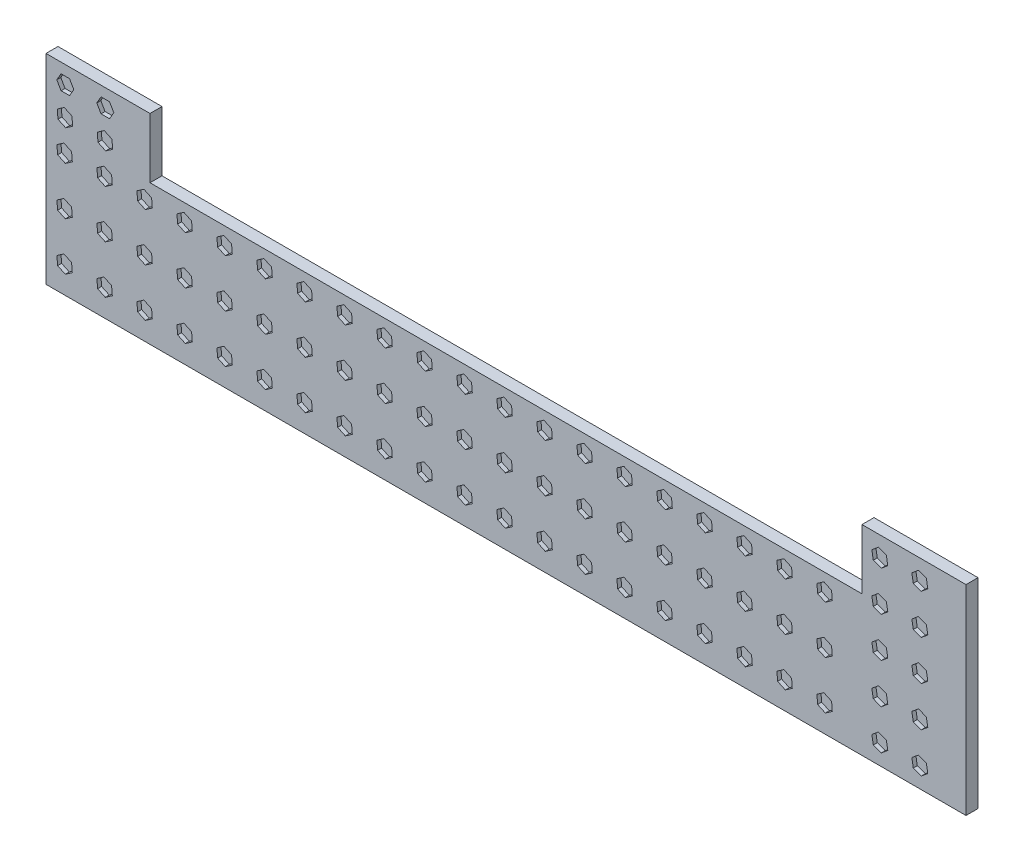
SolidWorks part; units mm, degrees
ref_plane "Front Plane" through (0, 0, 0) normal (0, 0, 1) x (1, 0, 0)
ref_plane "Top Plane" through (0, 0, 0) normal (0, 1, 0) x (1, 0, 0)
ref_plane "Right Plane" through (0, 0, 0) normal (1, 0, 0) x (0, 0, -1)
sketch "Sketch1" plane through (0, 0, 0) normal (0, 0, 1) x (1, 0, 0)
  line L6 (-151.2957, 20.8865) -> (-151.2957, -29.1135)
  line L7 (-151.2957, -29.1135) -> (78.7043, -29.1135)
  line L9 (78.7043, 20.8865) -> (78.7043, -29.1135)
  line L10 (-151.2957, 20.8865) -> (-125.2957, 20.8865)
  line L11 (-125.2957, 20.8865) -> (-125.2957, 5.8865)
  line L12 (-125.2957, 5.8865) -> (52.7043, 5.8865)
  line L13 (52.7043, 5.8865) -> (52.7043, 20.8865)
  line L14 (52.7043, 20.8865) -> (78.7043, 20.8865)
  dimension "D1" = 230
  dimension "D2" = 26
  dimension "D3" = 15
  dimension "D4" = 50
extrude "Boss-Extrude1" add sketch "Sketch1" along normal blind 3
sketch "Sketch2" plane through (0, 0, 3) normal (0, 0, 1) x (1, 0, 0)
  line L0 (69.1519, 15.1967) -> (68.7905, 17.2904)
  line L1 (-144.3473, 16.5251) -> (-145.4096, 18.3651)
  line L2 (-145.4096, 18.3651) -> (-147.5343, 18.3651)
  line L3 (-147.5343, 18.3651) -> (-148.5966, 16.5251)
  line L4 (-148.5966, 16.5251) -> (-147.5343, 14.6851)
  line L5 (-147.5343, 14.6851) -> (-145.4096, 14.6851)
  line L6 (-145.4096, 14.6851) -> (-144.3473, 16.5251)
  line L7 (59.1519, 15.1967) -> (58.7905, 17.2904)
  line L8 (58.7905, 17.2904) -> (56.7966, 18.0243)
  line L9 (56.7966, 18.0243) -> (55.1642, 16.6645)
  line L10 (55.1642, 16.6645) -> (55.5255, 14.5708)
  line L11 (55.5255, 14.5708) -> (57.5194, 13.8369)
  line L12 (57.5194, 13.8369) -> (59.1519, 15.1967)
  line L13 (-144.6353, 8.4459) -> (-144.813, 10.5631)
  line L14 (-144.813, 10.5631) -> (-146.7355, 11.4677)
  line L15 (-146.7355, 11.4677) -> (-148.4801, 10.2552)
  line L16 (-148.4801, 10.2552) -> (-148.3024, 8.138)
  line L17 (-148.3024, 8.138) -> (-146.38, 7.2333)
  line L18 (-146.38, 7.2333) -> (-144.6353, 8.4459)
  line L19 (68.7905, 17.2904) -> (66.7966, 18.0243)
  line L20 (66.7966, 18.0243) -> (65.1642, 16.6645)
  line L21 (65.1642, 16.6645) -> (65.5255, 14.5708)
  line L22 (65.5255, 14.5708) -> (67.5194, 13.8369)
  line L23 (67.5194, 13.8369) -> (69.1519, 15.1967)
  line L24 (69.1519, 5.1967) -> (68.7905, 7.2904)
  line L25 (68.7905, 7.2904) -> (66.7966, 8.0243)
  line L26 (66.7966, 8.0243) -> (65.1642, 6.6645)
  line L27 (65.1642, 6.6645) -> (65.5255, 4.5708)
  line L28 (65.5255, 4.5708) -> (67.5194, 3.8369)
  line L29 (67.5194, 3.8369) -> (69.1519, 5.1967)
  line L30 (69.1519, -4.8033) -> (68.7905, -2.7096)
  line L31 (68.7905, -2.7096) -> (66.7966, -1.9757)
  line L32 (66.7966, -1.9757) -> (65.1642, -3.3355)
  line L33 (65.1642, -3.3355) -> (65.5255, -5.4292)
  line L34 (65.5255, -5.4292) -> (67.5194, -6.1631)
  line L35 (67.5194, -6.1631) -> (69.1519, -4.8033)
  line L36 (69.1519, -14.8033) -> (68.7905, -12.7096)
  line L37 (68.7905, -12.7096) -> (66.7966, -11.9757)
  line L38 (66.7966, -11.9757) -> (65.1642, -13.3355)
  line L39 (65.1642, -13.3355) -> (65.5255, -15.4292)
  line L40 (65.5255, -15.4292) -> (67.5194, -16.1631)
  line L41 (67.5194, -16.1631) -> (69.1519, -14.8033)
  line L42 (69.1519, -24.8033) -> (68.7905, -22.7096)
  line L43 (68.7905, -22.7096) -> (66.7966, -21.9757)
  line L44 (66.7966, -21.9757) -> (65.1642, -23.3355)
  line L45 (65.1642, -23.3355) -> (65.5255, -25.4292)
  line L46 (65.5255, -25.4292) -> (67.5194, -26.1631)
  line L47 (67.5194, -26.1631) -> (69.1519, -24.8033)
  line L48 (59.1519, 5.1967) -> (58.7905, 7.2904)
  line L49 (58.7905, 7.2904) -> (56.7966, 8.0243)
  line L50 (56.7966, 8.0243) -> (55.1642, 6.6645)
  line L51 (55.1642, 6.6645) -> (55.5255, 4.5708)
  line L52 (55.5255, 4.5708) -> (57.5194, 3.8369)
  line L53 (57.5194, 3.8369) -> (59.1519, 5.1967)
  line L54 (59.1519, -4.8033) -> (58.7905, -2.7096)
  line L55 (58.7905, -2.7096) -> (56.7966, -1.9757)
  line L56 (56.7966, -1.9757) -> (55.1642, -3.3355)
  line L57 (55.1642, -3.3355) -> (55.5255, -5.4292)
  line L58 (55.5255, -5.4292) -> (57.5194, -6.1631)
  line L59 (57.5194, -6.1631) -> (59.1519, -4.8033)
  line L60 (59.1519, -14.8033) -> (58.7905, -12.7096)
  line L61 (58.7905, -12.7096) -> (56.7966, -11.9757)
  line L62 (56.7966, -11.9757) -> (55.1642, -13.3355)
  line L63 (55.1642, -13.3355) -> (55.5255, -15.4292)
  line L64 (55.5255, -15.4292) -> (57.5194, -16.1631)
  line L65 (57.5194, -16.1631) -> (59.1519, -14.8033)
  line L66 (59.1519, -24.8033) -> (58.7905, -22.7096)
  line L67 (58.7905, -22.7096) -> (56.7966, -21.9757)
  line L68 (56.7966, -21.9757) -> (55.1642, -23.3355)
  line L69 (55.1642, -23.3355) -> (55.5255, -25.4292)
  line L70 (55.5255, -25.4292) -> (57.5194, -26.1631)
  line L71 (57.5194, -26.1631) -> (59.1519, -24.8033)
  line L72 (-144.7223, 0.6978) -> (-144.9001, 2.815)
  line L73 (-144.9001, 2.815) -> (-146.8225, 3.7197)
  line L74 (-146.8225, 3.7197) -> (-148.5672, 2.5072)
  line L75 (-148.5672, 2.5072) -> (-148.3894, 0.39)
  line L76 (-148.3894, 0.39) -> (-146.467, -0.5147)
  line L77 (-146.467, -0.5147) -> (-144.7223, 0.6978)
  line L78 (-134.3473, 16.5251) -> (-135.4096, 18.3651)
  line L79 (-135.4096, 18.3651) -> (-137.5343, 18.3651)
  line L80 (-137.5343, 18.3651) -> (-138.5966, 16.5251)
  line L81 (-138.5966, 16.5251) -> (-137.5343, 14.6851)
  line L82 (-137.5343, 14.6851) -> (-135.4096, 14.6851)
  line L83 (-135.4096, 14.6851) -> (-134.3473, 16.5251)
  line L84 (-134.6353, 8.4459) -> (-134.813, 10.5631)
  line L85 (-134.813, 10.5631) -> (-136.7355, 11.4677)
  line L86 (-136.7355, 11.4677) -> (-138.4801, 10.2552)
  line L87 (-138.4801, 10.2552) -> (-138.3024, 8.138)
  line L88 (-138.3024, 8.138) -> (-136.38, 7.2333)
  line L89 (-136.38, 7.2333) -> (-134.6353, 8.4459)
  line L90 (-134.7223, 0.6978) -> (-134.9001, 2.815)
  line L91 (-134.9001, 2.815) -> (-136.8225, 3.7197)
  line L92 (-136.8225, 3.7197) -> (-138.5672, 2.5072)
  line L93 (-138.5672, 2.5072) -> (-138.3894, 0.39)
  line L94 (-138.3894, 0.39) -> (-136.467, -0.5147)
  line L95 (-136.467, -0.5147) -> (-134.7223, 0.6978)
  line L96 (-124.7223, 0.6978) -> (-124.9001, 2.815)
  line L97 (-124.9001, 2.815) -> (-126.8225, 3.7197)
  line L98 (-126.8225, 3.7197) -> (-128.5672, 2.5072)
  line L99 (-128.5672, 2.5072) -> (-128.3894, 0.39)
  line L100 (-128.3894, 0.39) -> (-126.467, -0.5147)
  line L101 (-126.467, -0.5147) -> (-124.7223, 0.6978)
  line L102 (-114.7223, 0.6978) -> (-114.9001, 2.815)
  line L103 (-114.9001, 2.815) -> (-116.8225, 3.7197)
  line L104 (-116.8225, 3.7197) -> (-118.5672, 2.5072)
  line L105 (-118.5672, 2.5072) -> (-118.3894, 0.39)
  line L106 (-118.3894, 0.39) -> (-116.467, -0.5147)
  line L107 (-116.467, -0.5147) -> (-114.7223, 0.6978)
  line L108 (-104.7223, 0.6978) -> (-104.9001, 2.815)
  line L109 (-104.9001, 2.815) -> (-106.8225, 3.7197)
  line L110 (-106.8225, 3.7197) -> (-108.5672, 2.5072)
  line L111 (-108.5672, 2.5072) -> (-108.3894, 0.39)
  line L112 (-108.3894, 0.39) -> (-106.467, -0.5147)
  line L113 (-106.467, -0.5147) -> (-104.7223, 0.6978)
  line L114 (-94.7223, 0.6978) -> (-94.9001, 2.815)
  line L115 (-94.9001, 2.815) -> (-96.8225, 3.7197)
  line L116 (-96.8225, 3.7197) -> (-98.5672, 2.5072)
  line L117 (-98.5672, 2.5072) -> (-98.3894, 0.39)
  line L118 (-98.3894, 0.39) -> (-96.467, -0.5147)
  line L119 (-96.467, -0.5147) -> (-94.7223, 0.6978)
  line L120 (-84.7223, 0.6978) -> (-84.9001, 2.815)
  line L121 (-84.9001, 2.815) -> (-86.8225, 3.7197)
  line L122 (-86.8225, 3.7197) -> (-88.5672, 2.5072)
  line L123 (-88.5672, 2.5072) -> (-88.3894, 0.39)
  line L124 (-88.3894, 0.39) -> (-86.467, -0.5147)
  line L125 (-86.467, -0.5147) -> (-84.7223, 0.6978)
  line L126 (-74.7223, 0.6978) -> (-74.9001, 2.815)
  line L127 (-74.9001, 2.815) -> (-76.8225, 3.7197)
  line L128 (-76.8225, 3.7197) -> (-78.5672, 2.5072)
  line L129 (-78.5672, 2.5072) -> (-78.3894, 0.39)
  line L130 (-78.3894, 0.39) -> (-76.467, -0.5147)
  line L131 (-76.467, -0.5147) -> (-74.7223, 0.6978)
  line L132 (-64.7223, 0.6978) -> (-64.9001, 2.815)
  line L133 (-64.9001, 2.815) -> (-66.8225, 3.7197)
  line L134 (-66.8225, 3.7197) -> (-68.5672, 2.5072)
  line L135 (-68.5672, 2.5072) -> (-68.3894, 0.39)
  line L136 (-68.3894, 0.39) -> (-66.467, -0.5147)
  line L137 (-66.467, -0.5147) -> (-64.7223, 0.6978)
  line L138 (-54.7223, 0.6978) -> (-54.9001, 2.815)
  line L139 (-54.9001, 2.815) -> (-56.8225, 3.7197)
  line L140 (-56.8225, 3.7197) -> (-58.5672, 2.5072)
  line L141 (-58.5672, 2.5072) -> (-58.3894, 0.39)
  line L142 (-58.3894, 0.39) -> (-56.467, -0.5147)
  line L143 (-56.467, -0.5147) -> (-54.7223, 0.6978)
  line L144 (-44.7223, 0.6978) -> (-44.9001, 2.815)
  line L145 (-44.9001, 2.815) -> (-46.8225, 3.7197)
  line L146 (-46.8225, 3.7197) -> (-48.5672, 2.5072)
  line L147 (-48.5672, 2.5072) -> (-48.3894, 0.39)
  line L148 (-48.3894, 0.39) -> (-46.467, -0.5147)
  line L149 (-46.467, -0.5147) -> (-44.7223, 0.6978)
  line L150 (-34.7223, 0.6978) -> (-34.9001, 2.815)
  line L151 (-34.9001, 2.815) -> (-36.8225, 3.7197)
  line L152 (-36.8225, 3.7197) -> (-38.5672, 2.5072)
  line L153 (-38.5672, 2.5072) -> (-38.3894, 0.39)
  line L154 (-38.3894, 0.39) -> (-36.467, -0.5147)
  line L155 (-36.467, -0.5147) -> (-34.7223, 0.6978)
  line L156 (-24.7223, 0.6978) -> (-24.9001, 2.815)
  line L157 (-24.9001, 2.815) -> (-26.8225, 3.7197)
  line L158 (-26.8225, 3.7197) -> (-28.5672, 2.5072)
  line L159 (-28.5672, 2.5072) -> (-28.3894, 0.39)
  line L160 (-28.3894, 0.39) -> (-26.467, -0.5147)
  line L161 (-26.467, -0.5147) -> (-24.7223, 0.6978)
  line L162 (-14.7223, 0.6978) -> (-14.9001, 2.815)
  line L163 (-14.9001, 2.815) -> (-16.8225, 3.7197)
  line L164 (-16.8225, 3.7197) -> (-18.5672, 2.5072)
  line L165 (-18.5672, 2.5072) -> (-18.3894, 0.39)
  line L166 (-18.3894, 0.39) -> (-16.467, -0.5147)
  line L167 (-16.467, -0.5147) -> (-14.7223, 0.6978)
  line L168 (-4.7223, 0.6978) -> (-4.9001, 2.815)
  line L169 (-4.9001, 2.815) -> (-6.8225, 3.7197)
  line L170 (-6.8225, 3.7197) -> (-8.5672, 2.5072)
  line L171 (-8.5672, 2.5072) -> (-8.3894, 0.39)
  line L172 (-8.3894, 0.39) -> (-6.467, -0.5147)
  line L173 (-6.467, -0.5147) -> (-4.7223, 0.6978)
  line L174 (5.2777, 0.6978) -> (5.0999, 2.815)
  line L175 (5.0999, 2.815) -> (3.1775, 3.7197)
  line L176 (3.1775, 3.7197) -> (1.4328, 2.5072)
  line L177 (1.4328, 2.5072) -> (1.6106, 0.39)
  line L178 (1.6106, 0.39) -> (3.533, -0.5147)
  line L179 (3.533, -0.5147) -> (5.2777, 0.6978)
  line L180 (15.2777, 0.6978) -> (15.0999, 2.815)
  line L181 (15.0999, 2.815) -> (13.1775, 3.7197)
  line L182 (13.1775, 3.7197) -> (11.4328, 2.5072)
  line L183 (11.4328, 2.5072) -> (11.6106, 0.39)
  line L184 (11.6106, 0.39) -> (13.533, -0.5147)
  line L185 (13.533, -0.5147) -> (15.2777, 0.6978)
  line L186 (25.2777, 0.6978) -> (25.0999, 2.815)
  line L187 (25.0999, 2.815) -> (23.1775, 3.7197)
  line L188 (23.1775, 3.7197) -> (21.4328, 2.5072)
  line L189 (21.4328, 2.5072) -> (21.6106, 0.39)
  line L190 (21.6106, 0.39) -> (23.533, -0.5147)
  line L191 (23.533, -0.5147) -> (25.2777, 0.6978)
  line L192 (35.2777, 0.6978) -> (35.0999, 2.815)
  line L193 (35.0999, 2.815) -> (33.1775, 3.7197)
  line L194 (33.1775, 3.7197) -> (31.4328, 2.5072)
  line L195 (31.4328, 2.5072) -> (31.6106, 0.39)
  line L196 (31.6106, 0.39) -> (33.533, -0.5147)
  line L197 (33.533, -0.5147) -> (35.2777, 0.6978)
  line L198 (45.2777, 0.6978) -> (45.0999, 2.815)
  line L199 (45.0999, 2.815) -> (43.1775, 3.7197)
  line L200 (43.1775, 3.7197) -> (41.4328, 2.5072)
  line L201 (41.4328, 2.5072) -> (41.6106, 0.39)
  line L202 (41.6106, 0.39) -> (43.533, -0.5147)
  line L203 (43.533, -0.5147) -> (45.2777, 0.6978)
  line L204 (-134.7223, -11.3022) -> (-134.9001, -9.185)
  line L205 (-134.9001, -9.185) -> (-136.8225, -8.2803)
  line L206 (-136.8225, -8.2803) -> (-138.5672, -9.4928)
  line L207 (-138.5672, -9.4928) -> (-138.3894, -11.61)
  line L208 (-138.3894, -11.61) -> (-136.467, -12.5147)
  line L209 (-136.467, -12.5147) -> (-134.7223, -11.3022)
  line L210 (-124.7223, -11.3022) -> (-124.9001, -9.185)
  line L211 (-124.9001, -9.185) -> (-126.8225, -8.2803)
  line L212 (-126.8225, -8.2803) -> (-128.5672, -9.4928)
  line L213 (-128.5672, -9.4928) -> (-128.3894, -11.61)
  line L214 (-128.3894, -11.61) -> (-126.467, -12.5147)
  line L215 (-126.467, -12.5147) -> (-124.7223, -11.3022)
  line L216 (-114.7223, -11.3022) -> (-114.9001, -9.185)
  line L217 (-114.9001, -9.185) -> (-116.8225, -8.2803)
  line L218 (-116.8225, -8.2803) -> (-118.5672, -9.4928)
  line L219 (-118.5672, -9.4928) -> (-118.3894, -11.61)
  line L220 (-118.3894, -11.61) -> (-116.467, -12.5147)
  line L221 (-116.467, -12.5147) -> (-114.7223, -11.3022)
  line L222 (-104.7223, -11.3022) -> (-104.9001, -9.185)
  line L223 (-104.9001, -9.185) -> (-106.8225, -8.2803)
  line L224 (-106.8225, -8.2803) -> (-108.5672, -9.4928)
  line L225 (-108.5672, -9.4928) -> (-108.3894, -11.61)
  line L226 (-108.3894, -11.61) -> (-106.467, -12.5147)
  line L227 (-106.467, -12.5147) -> (-104.7223, -11.3022)
  line L228 (-94.7223, -11.3022) -> (-94.9001, -9.185)
  line L229 (-94.9001, -9.185) -> (-96.8225, -8.2803)
  line L230 (-96.8225, -8.2803) -> (-98.5672, -9.4928)
  line L231 (-98.5672, -9.4928) -> (-98.3894, -11.61)
  line L232 (-98.3894, -11.61) -> (-96.467, -12.5147)
  line L233 (-96.467, -12.5147) -> (-94.7223, -11.3022)
  line L234 (-84.7223, -11.3022) -> (-84.9001, -9.185)
  line L235 (-84.9001, -9.185) -> (-86.8225, -8.2803)
  line L236 (-86.8225, -8.2803) -> (-88.5672, -9.4928)
  line L237 (-88.5672, -9.4928) -> (-88.3894, -11.61)
  line L238 (-88.3894, -11.61) -> (-86.467, -12.5147)
  line L239 (-86.467, -12.5147) -> (-84.7223, -11.3022)
  line L240 (-74.7223, -11.3022) -> (-74.9001, -9.185)
  line L241 (-74.9001, -9.185) -> (-76.8225, -8.2803)
  line L242 (-76.8225, -8.2803) -> (-78.5672, -9.4928)
  line L243 (-78.5672, -9.4928) -> (-78.3894, -11.61)
  line L244 (-78.3894, -11.61) -> (-76.467, -12.5147)
  line L245 (-76.467, -12.5147) -> (-74.7223, -11.3022)
  line L246 (-64.7223, -11.3022) -> (-64.9001, -9.185)
  line L247 (-64.9001, -9.185) -> (-66.8225, -8.2803)
  line L248 (-66.8225, -8.2803) -> (-68.5672, -9.4928)
  line L249 (-68.5672, -9.4928) -> (-68.3894, -11.61)
  line L250 (-68.3894, -11.61) -> (-66.467, -12.5147)
  line L251 (-66.467, -12.5147) -> (-64.7223, -11.3022)
  line L252 (-54.7223, -11.3022) -> (-54.9001, -9.185)
  line L253 (-54.9001, -9.185) -> (-56.8225, -8.2803)
  line L254 (-56.8225, -8.2803) -> (-58.5672, -9.4928)
  line L255 (-58.5672, -9.4928) -> (-58.3894, -11.61)
  line L256 (-58.3894, -11.61) -> (-56.467, -12.5147)
  line L257 (-56.467, -12.5147) -> (-54.7223, -11.3022)
  line L258 (-44.7223, -11.3022) -> (-44.9001, -9.185)
  line L259 (-44.9001, -9.185) -> (-46.8225, -8.2803)
  line L260 (-46.8225, -8.2803) -> (-48.5672, -9.4928)
  line L261 (-48.5672, -9.4928) -> (-48.3894, -11.61)
  line L262 (-48.3894, -11.61) -> (-46.467, -12.5147)
  line L263 (-46.467, -12.5147) -> (-44.7223, -11.3022)
  line L264 (-34.7223, -11.3022) -> (-34.9001, -9.185)
  line L265 (-34.9001, -9.185) -> (-36.8225, -8.2803)
  line L266 (-36.8225, -8.2803) -> (-38.5672, -9.4928)
  line L267 (-38.5672, -9.4928) -> (-38.3894, -11.61)
  line L268 (-38.3894, -11.61) -> (-36.467, -12.5147)
  line L269 (-36.467, -12.5147) -> (-34.7223, -11.3022)
  line L270 (-24.7223, -11.3022) -> (-24.9001, -9.185)
  line L271 (-24.9001, -9.185) -> (-26.8225, -8.2803)
  line L272 (-26.8225, -8.2803) -> (-28.5672, -9.4928)
  line L273 (-28.5672, -9.4928) -> (-28.3894, -11.61)
  line L274 (-28.3894, -11.61) -> (-26.467, -12.5147)
  line L275 (-26.467, -12.5147) -> (-24.7223, -11.3022)
  line L276 (-14.7223, -11.3022) -> (-14.9001, -9.185)
  line L277 (-14.9001, -9.185) -> (-16.8225, -8.2803)
  line L278 (-16.8225, -8.2803) -> (-18.5672, -9.4928)
  line L279 (-18.5672, -9.4928) -> (-18.3894, -11.61)
  line L280 (-18.3894, -11.61) -> (-16.467, -12.5147)
  line L281 (-16.467, -12.5147) -> (-14.7223, -11.3022)
  line L282 (-4.7223, -11.3022) -> (-4.9001, -9.185)
  line L283 (-4.9001, -9.185) -> (-6.8225, -8.2803)
  line L284 (-6.8225, -8.2803) -> (-8.5672, -9.4928)
  line L285 (-8.5672, -9.4928) -> (-8.3894, -11.61)
  line L286 (-8.3894, -11.61) -> (-6.467, -12.5147)
  line L287 (-6.467, -12.5147) -> (-4.7223, -11.3022)
  line L288 (5.2777, -11.3022) -> (5.0999, -9.185)
  line L289 (5.0999, -9.185) -> (3.1775, -8.2803)
  line L290 (3.1775, -8.2803) -> (1.4328, -9.4928)
  line L291 (1.4328, -9.4928) -> (1.6106, -11.61)
  line L292 (1.6106, -11.61) -> (3.533, -12.5147)
  line L293 (3.533, -12.5147) -> (5.2777, -11.3022)
  line L294 (15.2777, -11.3022) -> (15.0999, -9.185)
  line L295 (15.0999, -9.185) -> (13.1775, -8.2803)
  line L296 (13.1775, -8.2803) -> (11.4328, -9.4928)
  line L297 (11.4328, -9.4928) -> (11.6106, -11.61)
  line L298 (11.6106, -11.61) -> (13.533, -12.5147)
  line L299 (13.533, -12.5147) -> (15.2777, -11.3022)
  line L300 (25.2777, -11.3022) -> (25.0999, -9.185)
  line L301 (25.0999, -9.185) -> (23.1775, -8.2803)
  line L302 (23.1775, -8.2803) -> (21.4328, -9.4928)
  line L303 (21.4328, -9.4928) -> (21.6106, -11.61)
  line L304 (21.6106, -11.61) -> (23.533, -12.5147)
  line L305 (23.533, -12.5147) -> (25.2777, -11.3022)
  line L306 (35.2777, -11.3022) -> (35.0999, -9.185)
  line L307 (35.0999, -9.185) -> (33.1775, -8.2803)
  line L308 (33.1775, -8.2803) -> (31.4328, -9.4928)
  line L309 (31.4328, -9.4928) -> (31.6106, -11.61)
  line L310 (31.6106, -11.61) -> (33.533, -12.5147)
  line L311 (33.533, -12.5147) -> (35.2777, -11.3022)
  line L312 (45.2777, -11.3022) -> (45.0999, -9.185)
  line L313 (45.0999, -9.185) -> (43.1775, -8.2803)
  line L314 (43.1775, -8.2803) -> (41.4328, -9.4928)
  line L315 (41.4328, -9.4928) -> (41.6106, -11.61)
  line L316 (41.6106, -11.61) -> (43.533, -12.5147)
  line L317 (43.533, -12.5147) -> (45.2777, -11.3022)
  line L318 (-134.7223, -23.3022) -> (-134.9001, -21.185)
  line L319 (-134.9001, -21.185) -> (-136.8225, -20.2803)
  line L320 (-136.8225, -20.2803) -> (-138.5672, -21.4928)
  line L321 (-138.5672, -21.4928) -> (-138.3894, -23.61)
  line L322 (-138.3894, -23.61) -> (-136.467, -24.5147)
  line L323 (-136.467, -24.5147) -> (-134.7223, -23.3022)
  line L324 (-124.7223, -23.3022) -> (-124.9001, -21.185)
  line L325 (-124.9001, -21.185) -> (-126.8225, -20.2803)
  line L326 (-126.8225, -20.2803) -> (-128.5672, -21.4928)
  line L327 (-128.5672, -21.4928) -> (-128.3894, -23.61)
  line L328 (-128.3894, -23.61) -> (-126.467, -24.5147)
  line L329 (-126.467, -24.5147) -> (-124.7223, -23.3022)
  line L330 (-114.7223, -23.3022) -> (-114.9001, -21.185)
  line L331 (-114.9001, -21.185) -> (-116.8225, -20.2803)
  line L332 (-116.8225, -20.2803) -> (-118.5672, -21.4928)
  line L333 (-118.5672, -21.4928) -> (-118.3894, -23.61)
  line L334 (-118.3894, -23.61) -> (-116.467, -24.5147)
  line L335 (-116.467, -24.5147) -> (-114.7223, -23.3022)
  line L336 (-104.7223, -23.3022) -> (-104.9001, -21.185)
  line L337 (-104.9001, -21.185) -> (-106.8225, -20.2803)
  line L338 (-106.8225, -20.2803) -> (-108.5672, -21.4928)
  line L339 (-108.5672, -21.4928) -> (-108.3894, -23.61)
  line L340 (-108.3894, -23.61) -> (-106.467, -24.5147)
  line L341 (-106.467, -24.5147) -> (-104.7223, -23.3022)
  line L342 (-94.7223, -23.3022) -> (-94.9001, -21.185)
  line L343 (-94.9001, -21.185) -> (-96.8225, -20.2803)
  line L344 (-96.8225, -20.2803) -> (-98.5672, -21.4928)
  line L345 (-98.5672, -21.4928) -> (-98.3894, -23.61)
  line L346 (-98.3894, -23.61) -> (-96.467, -24.5147)
  line L347 (-96.467, -24.5147) -> (-94.7223, -23.3022)
  line L348 (-84.7223, -23.3022) -> (-84.9001, -21.185)
  line L349 (-84.9001, -21.185) -> (-86.8225, -20.2803)
  line L350 (-86.8225, -20.2803) -> (-88.5672, -21.4928)
  line L351 (-88.5672, -21.4928) -> (-88.3894, -23.61)
  line L352 (-88.3894, -23.61) -> (-86.467, -24.5147)
  line L353 (-86.467, -24.5147) -> (-84.7223, -23.3022)
  line L354 (-74.7223, -23.3022) -> (-74.9001, -21.185)
  line L355 (-74.9001, -21.185) -> (-76.8225, -20.2803)
  line L356 (-76.8225, -20.2803) -> (-78.5672, -21.4928)
  line L357 (-78.5672, -21.4928) -> (-78.3894, -23.61)
  line L358 (-78.3894, -23.61) -> (-76.467, -24.5147)
  line L359 (-76.467, -24.5147) -> (-74.7223, -23.3022)
  line L360 (-64.7223, -23.3022) -> (-64.9001, -21.185)
  line L361 (-64.9001, -21.185) -> (-66.8225, -20.2803)
  line L362 (-66.8225, -20.2803) -> (-68.5672, -21.4928)
  line L363 (-68.5672, -21.4928) -> (-68.3894, -23.61)
  line L364 (-68.3894, -23.61) -> (-66.467, -24.5147)
  line L365 (-66.467, -24.5147) -> (-64.7223, -23.3022)
  line L366 (-54.7223, -23.3022) -> (-54.9001, -21.185)
  line L367 (-54.9001, -21.185) -> (-56.8225, -20.2803)
  line L368 (-56.8225, -20.2803) -> (-58.5672, -21.4928)
  line L369 (-58.5672, -21.4928) -> (-58.3894, -23.61)
  line L370 (-58.3894, -23.61) -> (-56.467, -24.5147)
  line L371 (-56.467, -24.5147) -> (-54.7223, -23.3022)
  line L372 (-44.7223, -23.3022) -> (-44.9001, -21.185)
  line L373 (-44.9001, -21.185) -> (-46.8225, -20.2803)
  line L374 (-46.8225, -20.2803) -> (-48.5672, -21.4928)
  line L375 (-48.5672, -21.4928) -> (-48.3894, -23.61)
  line L376 (-48.3894, -23.61) -> (-46.467, -24.5147)
  line L377 (-46.467, -24.5147) -> (-44.7223, -23.3022)
  line L378 (-34.7223, -23.3022) -> (-34.9001, -21.185)
  line L379 (-34.9001, -21.185) -> (-36.8225, -20.2803)
  line L380 (-36.8225, -20.2803) -> (-38.5672, -21.4928)
  line L381 (-38.5672, -21.4928) -> (-38.3894, -23.61)
  line L382 (-38.3894, -23.61) -> (-36.467, -24.5147)
  line L383 (-36.467, -24.5147) -> (-34.7223, -23.3022)
  line L384 (-24.7223, -23.3022) -> (-24.9001, -21.185)
  line L385 (-24.9001, -21.185) -> (-26.8225, -20.2803)
  line L386 (-26.8225, -20.2803) -> (-28.5672, -21.4928)
  line L387 (-28.5672, -21.4928) -> (-28.3894, -23.61)
  line L388 (-28.3894, -23.61) -> (-26.467, -24.5147)
  line L389 (-26.467, -24.5147) -> (-24.7223, -23.3022)
  line L390 (-14.7223, -23.3022) -> (-14.9001, -21.185)
  line L391 (-14.9001, -21.185) -> (-16.8225, -20.2803)
  line L392 (-16.8225, -20.2803) -> (-18.5672, -21.4928)
  line L393 (-18.5672, -21.4928) -> (-18.3894, -23.61)
  line L394 (-18.3894, -23.61) -> (-16.467, -24.5147)
  line L395 (-16.467, -24.5147) -> (-14.7223, -23.3022)
  line L396 (-4.7223, -23.3022) -> (-4.9001, -21.185)
  line L397 (-4.9001, -21.185) -> (-6.8225, -20.2803)
  line L398 (-6.8225, -20.2803) -> (-8.5672, -21.4928)
  line L399 (-8.5672, -21.4928) -> (-8.3894, -23.61)
  line L400 (-8.3894, -23.61) -> (-6.467, -24.5147)
  line L401 (-6.467, -24.5147) -> (-4.7223, -23.3022)
  line L402 (5.2777, -23.3022) -> (5.0999, -21.185)
  line L403 (5.0999, -21.185) -> (3.1775, -20.2803)
  line L404 (3.1775, -20.2803) -> (1.4328, -21.4928)
  line L405 (1.4328, -21.4928) -> (1.6106, -23.61)
  line L406 (1.6106, -23.61) -> (3.533, -24.5147)
  line L407 (3.533, -24.5147) -> (5.2777, -23.3022)
  line L408 (15.2777, -23.3022) -> (15.0999, -21.185)
  line L409 (15.0999, -21.185) -> (13.1775, -20.2803)
  line L410 (13.1775, -20.2803) -> (11.4328, -21.4928)
  line L411 (11.4328, -21.4928) -> (11.6106, -23.61)
  line L412 (11.6106, -23.61) -> (13.533, -24.5147)
  line L413 (13.533, -24.5147) -> (15.2777, -23.3022)
  line L414 (25.2777, -23.3022) -> (25.0999, -21.185)
  line L415 (25.0999, -21.185) -> (23.1775, -20.2803)
  line L416 (23.1775, -20.2803) -> (21.4328, -21.4928)
  line L417 (21.4328, -21.4928) -> (21.6106, -23.61)
  line L418 (21.6106, -23.61) -> (23.533, -24.5147)
  line L419 (23.533, -24.5147) -> (25.2777, -23.3022)
  line L420 (35.2777, -23.3022) -> (35.0999, -21.185)
  line L421 (35.0999, -21.185) -> (33.1775, -20.2803)
  line L422 (33.1775, -20.2803) -> (31.4328, -21.4928)
  line L423 (31.4328, -21.4928) -> (31.6106, -23.61)
  line L424 (31.6106, -23.61) -> (33.533, -24.5147)
  line L425 (33.533, -24.5147) -> (35.2777, -23.3022)
  line L426 (45.2777, -23.3022) -> (45.0999, -21.185)
  line L427 (45.0999, -21.185) -> (43.1775, -20.2803)
  line L428 (43.1775, -20.2803) -> (41.4328, -21.4928)
  line L429 (41.4328, -21.4928) -> (41.6106, -23.61)
  line L430 (41.6106, -23.61) -> (43.533, -24.5147)
  line L431 (43.533, -24.5147) -> (45.2777, -23.3022)
  line L432 (-144.7223, -11.3022) -> (-144.9001, -9.185)
  line L433 (-144.9001, -9.185) -> (-146.8225, -8.2803)
  line L434 (-146.8225, -8.2803) -> (-148.5672, -9.4928)
  line L435 (-148.5672, -9.4928) -> (-148.3894, -11.61)
  line L436 (-148.3894, -11.61) -> (-146.467, -12.5147)
  line L437 (-146.467, -12.5147) -> (-144.7223, -11.3022)
  line L438 (-144.7223, -23.3022) -> (-144.9001, -21.185)
  line L439 (-144.9001, -21.185) -> (-146.8225, -20.2803)
  line L440 (-146.8225, -20.2803) -> (-148.5672, -21.4928)
  line L441 (-148.5672, -21.4928) -> (-148.3894, -23.61)
  line L442 (-148.3894, -23.61) -> (-146.467, -24.5147)
  line L443 (-146.467, -24.5147) -> (-144.7223, -23.3022)
  circle A0 centre (-146.4719, 16.5251) radius 1.84 construction
  circle A1 centre (57.158, 15.9306) radius 1.84 construction
  circle A2 centre (-146.5577, 9.3505) radius 1.84 construction
  dimension "D1" = 3.68
  dimension "D2" = 3.68
  dimension "D3" = 3.68
  dimension "D4" = 2
  dimension "D5" = 5
  dimension "D6" = 2
  dimension "D7" = 2
  dimension "D8" = 20
  dimension "D9" = 3
extrude "Cut-Extrude1" cut sketch "Sketch2" against normal blind 1
sketch "Sketch3" plane through (0, 0, 0) normal (0, 0, -1) x (-1, 0, 0)
  line L0 (133.46, 15.016) -> (133.9644, 17.0799)
  line L1 (-69.7509, 15.4518) -> (-70.0025, 17.5615)
  line L2 (-70.0025, 17.5615) -> (-71.9554, 18.3984)
  line L3 (-71.9554, 18.3984) -> (-73.6566, 17.1257)
  line L4 (-73.6566, 17.1257) -> (-73.405, 15.016)
  line L5 (-73.405, 15.016) -> (-71.4522, 14.179)
  line L6 (-71.4522, 14.179) -> (-69.7509, 15.4518)
  line L7 (-69.6794, 4.5396) -> (-69.6848, 6.6642)
  line L8 (-69.6848, 6.6642) -> (-71.5275, 7.7219)
  line L9 (-71.5275, 7.7219) -> (-73.3648, 6.6548)
  line L10 (-73.3648, 6.6548) -> (-73.3594, 4.5302)
  line L11 (-73.3594, 4.5302) -> (-71.5167, 3.4726)
  line L12 (-71.5167, 3.4726) -> (-69.6794, 4.5396)
  line L13 (-69.4772, -5.895) -> (-68.9728, -3.831)
  line L14 (-68.9728, -3.831) -> (-70.5081, -2.3623)
  line L15 (-70.5081, -2.3623) -> (-72.5476, -2.9575)
  line L16 (-72.5476, -2.9575) -> (-73.052, -5.0214)
  line L17 (-73.052, -5.0214) -> (-71.5168, -6.4901)
  line L18 (-71.5168, -6.4901) -> (-69.4772, -5.895)
  line L19 (134.7953, 6.0092) -> (133.733, 7.8492)
  line L20 (133.733, 7.8492) -> (131.6083, 7.8492)
  line L21 (131.6083, 7.8492) -> (130.546, 6.0092)
  line L22 (130.546, 6.0092) -> (131.6083, 4.1692)
  line L23 (131.6083, 4.1692) -> (133.733, 4.1692)
  line L24 (133.733, 4.1692) -> (134.7953, 6.0092)
  line L25 (133.9644, 17.0799) -> (132.4292, 18.5486)
  line L26 (132.4292, 18.5486) -> (130.3896, 17.9535)
  line L27 (130.3896, 17.9535) -> (129.8852, 15.8895)
  line L28 (129.8852, 15.8895) -> (131.4204, 14.4208)
  line L29 (131.4204, 14.4208) -> (133.46, 15.016)
  line L30 (-59.7509, 15.4518) -> (-60.0025, 17.5615)
  line L31 (-60.0025, 17.5615) -> (-61.9554, 18.3984)
  line L32 (-61.9554, 18.3984) -> (-63.6566, 17.1257)
  line L33 (-63.6566, 17.1257) -> (-63.405, 15.016)
  line L34 (-63.405, 15.016) -> (-61.4522, 14.179)
  line L35 (-61.4522, 14.179) -> (-59.7509, 15.4518)
  line L36 (-59.6794, 4.5396) -> (-59.6848, 6.6642)
  line L37 (-59.6848, 6.6642) -> (-61.5275, 7.7219)
  line L38 (-61.5275, 7.7219) -> (-63.3648, 6.6548)
  line L39 (-63.3648, 6.6548) -> (-63.3594, 4.5302)
  line L40 (-63.3594, 4.5302) -> (-61.5167, 3.4726)
  line L41 (-61.5167, 3.4726) -> (-59.6794, 4.5396)
  line L42 (143.46, 15.016) -> (143.9644, 17.0799)
  line L43 (143.9644, 17.0799) -> (142.4292, 18.5486)
  line L44 (142.4292, 18.5486) -> (140.3896, 17.9535)
  line L45 (140.3896, 17.9535) -> (139.8852, 15.8895)
  line L46 (139.8852, 15.8895) -> (141.4204, 14.4208)
  line L47 (141.4204, 14.4208) -> (143.46, 15.016)
  line L48 (144.7953, 6.0092) -> (143.733, 7.8492)
  line L49 (143.733, 7.8492) -> (141.6083, 7.8492)
  line L50 (141.6083, 7.8492) -> (140.546, 6.0092)
  line L51 (140.546, 6.0092) -> (141.6083, 4.1692)
  line L52 (141.6083, 4.1692) -> (143.733, 4.1692)
  line L53 (143.733, 4.1692) -> (144.7953, 6.0092)
  line L54 (144.7953, -3.9908) -> (143.733, -2.1508)
  line L55 (143.733, -2.1508) -> (141.6083, -2.1508)
  line L56 (141.6083, -2.1508) -> (140.546, -3.9908)
  line L57 (140.546, -3.9908) -> (141.6083, -5.8308)
  line L58 (141.6083, -5.8308) -> (143.733, -5.8308)
  line L59 (143.733, -5.8308) -> (144.7953, -3.9908)
  line L60 (144.7953, -13.9908) -> (143.733, -12.1508)
  line L61 (143.733, -12.1508) -> (141.6083, -12.1508)
  line L62 (141.6083, -12.1508) -> (140.546, -13.9908)
  line L63 (140.546, -13.9908) -> (141.6083, -15.8308)
  line L64 (141.6083, -15.8308) -> (143.733, -15.8308)
  line L65 (143.733, -15.8308) -> (144.7953, -13.9908)
  line L66 (144.7953, -23.9908) -> (143.733, -22.1508)
  line L67 (143.733, -22.1508) -> (141.6083, -22.1508)
  line L68 (141.6083, -22.1508) -> (140.546, -23.9908)
  line L69 (140.546, -23.9908) -> (141.6083, -25.8308)
  line L70 (141.6083, -25.8308) -> (143.733, -25.8308)
  line L71 (143.733, -25.8308) -> (144.7953, -23.9908)
  line L72 (134.7953, -3.9908) -> (133.733, -2.1508)
  line L73 (133.733, -2.1508) -> (131.6083, -2.1508)
  line L74 (131.6083, -2.1508) -> (130.546, -3.9908)
  line L75 (130.546, -3.9908) -> (131.6083, -5.8308)
  line L76 (131.6083, -5.8308) -> (133.733, -5.8308)
  line L77 (133.733, -5.8308) -> (134.7953, -3.9908)
  line L78 (134.7953, -13.9908) -> (133.733, -12.1508)
  line L79 (133.733, -12.1508) -> (131.6083, -12.1508)
  line L80 (131.6083, -12.1508) -> (130.546, -13.9908)
  line L81 (130.546, -13.9908) -> (131.6083, -15.8308)
  line L82 (131.6083, -15.8308) -> (133.733, -15.8308)
  line L83 (133.733, -15.8308) -> (134.7953, -13.9908)
  line L84 (134.7953, -23.9908) -> (133.733, -22.1508)
  line L85 (133.733, -22.1508) -> (131.6083, -22.1508)
  line L86 (131.6083, -22.1508) -> (130.546, -23.9908)
  line L87 (130.546, -23.9908) -> (131.6083, -25.8308)
  line L88 (131.6083, -25.8308) -> (133.733, -25.8308)
  line L89 (133.733, -25.8308) -> (134.7953, -23.9908)
  line L90 (-59.4772, -5.895) -> (-58.9728, -3.831)
  line L91 (-58.9728, -3.831) -> (-60.5081, -2.3623)
  line L92 (-60.5081, -2.3623) -> (-62.5476, -2.9575)
  line L93 (-62.5476, -2.9575) -> (-63.052, -5.0214)
  line L94 (-63.052, -5.0214) -> (-61.5168, -6.4901)
  line L95 (-61.5168, -6.4901) -> (-59.4772, -5.895)
  line L96 (-49.4772, -5.895) -> (-48.9728, -3.831)
  line L97 (-48.9728, -3.831) -> (-50.5081, -2.3623)
  line L98 (-50.5081, -2.3623) -> (-52.5476, -2.9575)
  line L99 (-52.5476, -2.9575) -> (-53.052, -5.0214)
  line L100 (-53.052, -5.0214) -> (-51.5168, -6.4901)
  line L101 (-51.5168, -6.4901) -> (-49.4772, -5.895)
  line L102 (-39.4772, -5.895) -> (-38.9728, -3.831)
  line L103 (-38.9728, -3.831) -> (-40.5081, -2.3623)
  line L104 (-40.5081, -2.3623) -> (-42.5476, -2.9575)
  line L105 (-42.5476, -2.9575) -> (-43.052, -5.0214)
  line L106 (-43.052, -5.0214) -> (-41.5168, -6.4901)
  line L107 (-41.5168, -6.4901) -> (-39.4772, -5.895)
  line L108 (-29.4772, -5.895) -> (-28.9728, -3.831)
  line L109 (-28.9728, -3.831) -> (-30.5081, -2.3623)
  line L110 (-30.5081, -2.3623) -> (-32.5476, -2.9575)
  line L111 (-32.5476, -2.9575) -> (-33.052, -5.0214)
  line L112 (-33.052, -5.0214) -> (-31.5168, -6.4901)
  line L113 (-31.5168, -6.4901) -> (-29.4772, -5.895)
  line L114 (-19.4772, -5.895) -> (-18.9728, -3.831)
  line L115 (-18.9728, -3.831) -> (-20.5081, -2.3623)
  line L116 (-20.5081, -2.3623) -> (-22.5476, -2.9575)
  line L117 (-22.5476, -2.9575) -> (-23.052, -5.0214)
  line L118 (-23.052, -5.0214) -> (-21.5168, -6.4901)
  line L119 (-21.5168, -6.4901) -> (-19.4772, -5.895)
  line L120 (-9.4772, -5.895) -> (-8.9728, -3.831)
  line L121 (-8.9728, -3.831) -> (-10.5081, -2.3623)
  line L122 (-10.5081, -2.3623) -> (-12.5476, -2.9575)
  line L123 (-12.5476, -2.9575) -> (-13.052, -5.0214)
  line L124 (-13.052, -5.0214) -> (-11.5168, -6.4901)
  line L125 (-11.5168, -6.4901) -> (-9.4772, -5.895)
  line L126 (0.5228, -5.895) -> (1.0272, -3.831)
  line L127 (1.0272, -3.831) -> (-0.5081, -2.3623)
  line L128 (-0.5081, -2.3623) -> (-2.5476, -2.9575)
  line L129 (-2.5476, -2.9575) -> (-3.052, -5.0214)
  line L130 (-3.052, -5.0214) -> (-1.5168, -6.4901)
  line L131 (-1.5168, -6.4901) -> (0.5228, -5.895)
  line L132 (10.5228, -5.895) -> (11.0272, -3.831)
  line L133 (11.0272, -3.831) -> (9.4919, -2.3623)
  line L134 (9.4919, -2.3623) -> (7.4524, -2.9575)
  line L135 (7.4524, -2.9575) -> (6.948, -5.0214)
  line L136 (6.948, -5.0214) -> (8.4832, -6.4901)
  line L137 (8.4832, -6.4901) -> (10.5228, -5.895)
  line L138 (20.5228, -5.895) -> (21.0272, -3.831)
  line L139 (21.0272, -3.831) -> (19.4919, -2.3623)
  line L140 (19.4919, -2.3623) -> (17.4524, -2.9575)
  line L141 (17.4524, -2.9575) -> (16.948, -5.0214)
  line L142 (16.948, -5.0214) -> (18.4832, -6.4901)
  line L143 (18.4832, -6.4901) -> (20.5228, -5.895)
  line L144 (30.5228, -5.895) -> (31.0272, -3.831)
  line L145 (31.0272, -3.831) -> (29.4919, -2.3623)
  line L146 (29.4919, -2.3623) -> (27.4524, -2.9575)
  line L147 (27.4524, -2.9575) -> (26.948, -5.0214)
  line L148 (26.948, -5.0214) -> (28.4832, -6.4901)
  line L149 (28.4832, -6.4901) -> (30.5228, -5.895)
  line L150 (40.5228, -5.895) -> (41.0272, -3.831)
  line L151 (41.0272, -3.831) -> (39.4919, -2.3623)
  line L152 (39.4919, -2.3623) -> (37.4524, -2.9575)
  line L153 (37.4524, -2.9575) -> (36.948, -5.0214)
  line L154 (36.948, -5.0214) -> (38.4832, -6.4901)
  line L155 (38.4832, -6.4901) -> (40.5228, -5.895)
  line L156 (50.5228, -5.895) -> (51.0272, -3.831)
  line L157 (51.0272, -3.831) -> (49.4919, -2.3623)
  line L158 (49.4919, -2.3623) -> (47.4524, -2.9575)
  line L159 (47.4524, -2.9575) -> (46.948, -5.0214)
  line L160 (46.948, -5.0214) -> (48.4832, -6.4901)
  line L161 (48.4832, -6.4901) -> (50.5228, -5.895)
  line L162 (60.5228, -5.895) -> (61.0272, -3.831)
  line L163 (61.0272, -3.831) -> (59.4919, -2.3623)
  line L164 (59.4919, -2.3623) -> (57.4524, -2.9575)
  line L165 (57.4524, -2.9575) -> (56.948, -5.0214)
  line L166 (56.948, -5.0214) -> (58.4832, -6.4901)
  line L167 (58.4832, -6.4901) -> (60.5228, -5.895)
  line L168 (70.5228, -5.895) -> (71.0272, -3.831)
  line L169 (71.0272, -3.831) -> (69.4919, -2.3623)
  line L170 (69.4919, -2.3623) -> (67.4524, -2.9575)
  line L171 (67.4524, -2.9575) -> (66.948, -5.0214)
  line L172 (66.948, -5.0214) -> (68.4832, -6.4901)
  line L173 (68.4832, -6.4901) -> (70.5228, -5.895)
  line L174 (80.5228, -5.895) -> (81.0272, -3.831)
  line L175 (81.0272, -3.831) -> (79.4919, -2.3623)
  line L176 (79.4919, -2.3623) -> (77.4524, -2.9575)
  line L177 (77.4524, -2.9575) -> (76.948, -5.0214)
  line L178 (76.948, -5.0214) -> (78.4832, -6.4901)
  line L179 (78.4832, -6.4901) -> (80.5228, -5.895)
  line L180 (90.5228, -5.895) -> (91.0272, -3.831)
  line L181 (91.0272, -3.831) -> (89.4919, -2.3623)
  line L182 (89.4919, -2.3623) -> (87.4524, -2.9575)
  line L183 (87.4524, -2.9575) -> (86.948, -5.0214)
  line L184 (86.948, -5.0214) -> (88.4832, -6.4901)
  line L185 (88.4832, -6.4901) -> (90.5228, -5.895)
  line L186 (100.5228, -5.895) -> (101.0272, -3.831)
  line L187 (101.0272, -3.831) -> (99.4919, -2.3623)
  line L188 (99.4919, -2.3623) -> (97.4524, -2.9575)
  line L189 (97.4524, -2.9575) -> (96.948, -5.0214)
  line L190 (96.948, -5.0214) -> (98.4832, -6.4901)
  line L191 (98.4832, -6.4901) -> (100.5228, -5.895)
  line L192 (110.5228, -5.895) -> (111.0272, -3.831)
  line L193 (111.0272, -3.831) -> (109.4919, -2.3623)
  line L194 (109.4919, -2.3623) -> (107.4524, -2.9575)
  line L195 (107.4524, -2.9575) -> (106.948, -5.0214)
  line L196 (106.948, -5.0214) -> (108.4832, -6.4901)
  line L197 (108.4832, -6.4901) -> (110.5228, -5.895)
  line L198 (120.5228, -5.895) -> (121.0272, -3.831)
  line L199 (121.0272, -3.831) -> (119.4919, -2.3623)
  line L200 (119.4919, -2.3623) -> (117.4524, -2.9575)
  line L201 (117.4524, -2.9575) -> (116.948, -5.0214)
  line L202 (116.948, -5.0214) -> (118.4832, -6.4901)
  line L203 (118.4832, -6.4901) -> (120.5228, -5.895)
  line L204 (-59.4772, -15.895) -> (-58.9728, -13.831)
  line L205 (-58.9728, -13.831) -> (-60.5081, -12.3623)
  line L206 (-60.5081, -12.3623) -> (-62.5476, -12.9575)
  line L207 (-62.5476, -12.9575) -> (-63.052, -15.0214)
  line L208 (-63.052, -15.0214) -> (-61.5168, -16.4901)
  line L209 (-61.5168, -16.4901) -> (-59.4772, -15.895)
  line L210 (-49.4772, -15.895) -> (-48.9728, -13.831)
  line L211 (-48.9728, -13.831) -> (-50.5081, -12.3623)
  line L212 (-50.5081, -12.3623) -> (-52.5476, -12.9575)
  line L213 (-52.5476, -12.9575) -> (-53.052, -15.0214)
  line L214 (-53.052, -15.0214) -> (-51.5168, -16.4901)
  line L215 (-51.5168, -16.4901) -> (-49.4772, -15.895)
  line L216 (-39.4772, -15.895) -> (-38.9728, -13.831)
  line L217 (-38.9728, -13.831) -> (-40.5081, -12.3623)
  line L218 (-40.5081, -12.3623) -> (-42.5476, -12.9575)
  line L219 (-42.5476, -12.9575) -> (-43.052, -15.0214)
  line L220 (-43.052, -15.0214) -> (-41.5168, -16.4901)
  line L221 (-41.5168, -16.4901) -> (-39.4772, -15.895)
  line L222 (-29.4772, -15.895) -> (-28.9728, -13.831)
  line L223 (-28.9728, -13.831) -> (-30.5081, -12.3623)
  line L224 (-30.5081, -12.3623) -> (-32.5476, -12.9575)
  line L225 (-32.5476, -12.9575) -> (-33.052, -15.0214)
  line L226 (-33.052, -15.0214) -> (-31.5168, -16.4901)
  line L227 (-31.5168, -16.4901) -> (-29.4772, -15.895)
  line L228 (-19.4772, -15.895) -> (-18.9728, -13.831)
  line L229 (-18.9728, -13.831) -> (-20.5081, -12.3623)
  line L230 (-20.5081, -12.3623) -> (-22.5476, -12.9575)
  line L231 (-22.5476, -12.9575) -> (-23.052, -15.0214)
  line L232 (-23.052, -15.0214) -> (-21.5168, -16.4901)
  line L233 (-21.5168, -16.4901) -> (-19.4772, -15.895)
  line L234 (-9.4772, -15.895) -> (-8.9728, -13.831)
  line L235 (-8.9728, -13.831) -> (-10.5081, -12.3623)
  line L236 (-10.5081, -12.3623) -> (-12.5476, -12.9575)
  line L237 (-12.5476, -12.9575) -> (-13.052, -15.0214)
  line L238 (-13.052, -15.0214) -> (-11.5168, -16.4901)
  line L239 (-11.5168, -16.4901) -> (-9.4772, -15.895)
  line L240 (0.5228, -15.895) -> (1.0272, -13.831)
  line L241 (1.0272, -13.831) -> (-0.5081, -12.3623)
  line L242 (-0.5081, -12.3623) -> (-2.5476, -12.9575)
  line L243 (-2.5476, -12.9575) -> (-3.052, -15.0214)
  line L244 (-3.052, -15.0214) -> (-1.5168, -16.4901)
  line L245 (-1.5168, -16.4901) -> (0.5228, -15.895)
  line L246 (10.5228, -15.895) -> (11.0272, -13.831)
  line L247 (11.0272, -13.831) -> (9.4919, -12.3623)
  line L248 (9.4919, -12.3623) -> (7.4524, -12.9575)
  line L249 (7.4524, -12.9575) -> (6.948, -15.0214)
  line L250 (6.948, -15.0214) -> (8.4832, -16.4901)
  line L251 (8.4832, -16.4901) -> (10.5228, -15.895)
  line L252 (20.5228, -15.895) -> (21.0272, -13.831)
  line L253 (21.0272, -13.831) -> (19.4919, -12.3623)
  line L254 (19.4919, -12.3623) -> (17.4524, -12.9575)
  line L255 (17.4524, -12.9575) -> (16.948, -15.0214)
  line L256 (16.948, -15.0214) -> (18.4832, -16.4901)
  line L257 (18.4832, -16.4901) -> (20.5228, -15.895)
  line L258 (30.5228, -15.895) -> (31.0272, -13.831)
  line L259 (31.0272, -13.831) -> (29.4919, -12.3623)
  line L260 (29.4919, -12.3623) -> (27.4524, -12.9575)
  line L261 (27.4524, -12.9575) -> (26.948, -15.0214)
  line L262 (26.948, -15.0214) -> (28.4832, -16.4901)
  line L263 (28.4832, -16.4901) -> (30.5228, -15.895)
  line L264 (40.5228, -15.895) -> (41.0272, -13.831)
  line L265 (41.0272, -13.831) -> (39.4919, -12.3623)
  line L266 (39.4919, -12.3623) -> (37.4524, -12.9575)
  line L267 (37.4524, -12.9575) -> (36.948, -15.0214)
  line L268 (36.948, -15.0214) -> (38.4832, -16.4901)
  line L269 (38.4832, -16.4901) -> (40.5228, -15.895)
  line L270 (50.5228, -15.895) -> (51.0272, -13.831)
  line L271 (51.0272, -13.831) -> (49.4919, -12.3623)
  line L272 (49.4919, -12.3623) -> (47.4524, -12.9575)
  line L273 (47.4524, -12.9575) -> (46.948, -15.0214)
  line L274 (46.948, -15.0214) -> (48.4832, -16.4901)
  line L275 (48.4832, -16.4901) -> (50.5228, -15.895)
  line L276 (60.5228, -15.895) -> (61.0272, -13.831)
  line L277 (61.0272, -13.831) -> (59.4919, -12.3623)
  line L278 (59.4919, -12.3623) -> (57.4524, -12.9575)
  line L279 (57.4524, -12.9575) -> (56.948, -15.0214)
  line L280 (56.948, -15.0214) -> (58.4832, -16.4901)
  line L281 (58.4832, -16.4901) -> (60.5228, -15.895)
  line L282 (70.5228, -15.895) -> (71.0272, -13.831)
  line L283 (71.0272, -13.831) -> (69.4919, -12.3623)
  line L284 (69.4919, -12.3623) -> (67.4524, -12.9575)
  line L285 (67.4524, -12.9575) -> (66.948, -15.0214)
  line L286 (66.948, -15.0214) -> (68.4832, -16.4901)
  line L287 (68.4832, -16.4901) -> (70.5228, -15.895)
  line L288 (80.5228, -15.895) -> (81.0272, -13.831)
  line L289 (81.0272, -13.831) -> (79.4919, -12.3623)
  line L290 (79.4919, -12.3623) -> (77.4524, -12.9575)
  line L291 (77.4524, -12.9575) -> (76.948, -15.0214)
  line L292 (76.948, -15.0214) -> (78.4832, -16.4901)
  line L293 (78.4832, -16.4901) -> (80.5228, -15.895)
  line L294 (90.5228, -15.895) -> (91.0272, -13.831)
  line L295 (91.0272, -13.831) -> (89.4919, -12.3623)
  line L296 (89.4919, -12.3623) -> (87.4524, -12.9575)
  line L297 (87.4524, -12.9575) -> (86.948, -15.0214)
  line L298 (86.948, -15.0214) -> (88.4832, -16.4901)
  line L299 (88.4832, -16.4901) -> (90.5228, -15.895)
  line L300 (100.5228, -15.895) -> (101.0272, -13.831)
  line L301 (101.0272, -13.831) -> (99.4919, -12.3623)
  line L302 (99.4919, -12.3623) -> (97.4524, -12.9575)
  line L303 (97.4524, -12.9575) -> (96.948, -15.0214)
  line L304 (96.948, -15.0214) -> (98.4832, -16.4901)
  line L305 (98.4832, -16.4901) -> (100.5228, -15.895)
  line L306 (110.5228, -15.895) -> (111.0272, -13.831)
  line L307 (111.0272, -13.831) -> (109.4919, -12.3623)
  line L308 (109.4919, -12.3623) -> (107.4524, -12.9575)
  line L309 (107.4524, -12.9575) -> (106.948, -15.0214)
  line L310 (106.948, -15.0214) -> (108.4832, -16.4901)
  line L311 (108.4832, -16.4901) -> (110.5228, -15.895)
  line L312 (120.5228, -15.895) -> (121.0272, -13.831)
  line L313 (121.0272, -13.831) -> (119.4919, -12.3623)
  line L314 (119.4919, -12.3623) -> (117.4524, -12.9575)
  line L315 (117.4524, -12.9575) -> (116.948, -15.0214)
  line L316 (116.948, -15.0214) -> (118.4832, -16.4901)
  line L317 (118.4832, -16.4901) -> (120.5228, -15.895)
  line L318 (-59.4772, -25.895) -> (-58.9728, -23.831)
  line L319 (-58.9728, -23.831) -> (-60.5081, -22.3623)
  line L320 (-60.5081, -22.3623) -> (-62.5476, -22.9575)
  line L321 (-62.5476, -22.9575) -> (-63.052, -25.0214)
  line L322 (-63.052, -25.0214) -> (-61.5168, -26.4901)
  line L323 (-61.5168, -26.4901) -> (-59.4772, -25.895)
  line L324 (-49.4772, -25.895) -> (-48.9728, -23.831)
  line L325 (-48.9728, -23.831) -> (-50.5081, -22.3623)
  line L326 (-50.5081, -22.3623) -> (-52.5476, -22.9575)
  line L327 (-52.5476, -22.9575) -> (-53.052, -25.0214)
  line L328 (-53.052, -25.0214) -> (-51.5168, -26.4901)
  line L329 (-51.5168, -26.4901) -> (-49.4772, -25.895)
  line L330 (-39.4772, -25.895) -> (-38.9728, -23.831)
  line L331 (-38.9728, -23.831) -> (-40.5081, -22.3623)
  line L332 (-40.5081, -22.3623) -> (-42.5476, -22.9575)
  line L333 (-42.5476, -22.9575) -> (-43.052, -25.0214)
  line L334 (-43.052, -25.0214) -> (-41.5168, -26.4901)
  line L335 (-41.5168, -26.4901) -> (-39.4772, -25.895)
  line L336 (-29.4772, -25.895) -> (-28.9728, -23.831)
  line L337 (-28.9728, -23.831) -> (-30.5081, -22.3623)
  line L338 (-30.5081, -22.3623) -> (-32.5476, -22.9575)
  line L339 (-32.5476, -22.9575) -> (-33.052, -25.0214)
  line L340 (-33.052, -25.0214) -> (-31.5168, -26.4901)
  line L341 (-31.5168, -26.4901) -> (-29.4772, -25.895)
  line L342 (-19.4772, -25.895) -> (-18.9728, -23.831)
  line L343 (-18.9728, -23.831) -> (-20.5081, -22.3623)
  line L344 (-20.5081, -22.3623) -> (-22.5476, -22.9575)
  line L345 (-22.5476, -22.9575) -> (-23.052, -25.0214)
  line L346 (-23.052, -25.0214) -> (-21.5168, -26.4901)
  line L347 (-21.5168, -26.4901) -> (-19.4772, -25.895)
  line L348 (-9.4772, -25.895) -> (-8.9728, -23.831)
  line L349 (-8.9728, -23.831) -> (-10.5081, -22.3623)
  line L350 (-10.5081, -22.3623) -> (-12.5476, -22.9575)
  line L351 (-12.5476, -22.9575) -> (-13.052, -25.0214)
  line L352 (-13.052, -25.0214) -> (-11.5168, -26.4901)
  line L353 (-11.5168, -26.4901) -> (-9.4772, -25.895)
  line L354 (0.5228, -25.895) -> (1.0272, -23.831)
  line L355 (1.0272, -23.831) -> (-0.5081, -22.3623)
  line L356 (-0.5081, -22.3623) -> (-2.5476, -22.9575)
  line L357 (-2.5476, -22.9575) -> (-3.052, -25.0214)
  line L358 (-3.052, -25.0214) -> (-1.5168, -26.4901)
  line L359 (-1.5168, -26.4901) -> (0.5228, -25.895)
  line L360 (10.5228, -25.895) -> (11.0272, -23.831)
  line L361 (11.0272, -23.831) -> (9.4919, -22.3623)
  line L362 (9.4919, -22.3623) -> (7.4524, -22.9575)
  line L363 (7.4524, -22.9575) -> (6.948, -25.0214)
  line L364 (6.948, -25.0214) -> (8.4832, -26.4901)
  line L365 (8.4832, -26.4901) -> (10.5228, -25.895)
  line L366 (20.5228, -25.895) -> (21.0272, -23.831)
  line L367 (21.0272, -23.831) -> (19.4919, -22.3623)
  line L368 (19.4919, -22.3623) -> (17.4524, -22.9575)
  line L369 (17.4524, -22.9575) -> (16.948, -25.0214)
  line L370 (16.948, -25.0214) -> (18.4832, -26.4901)
  line L371 (18.4832, -26.4901) -> (20.5228, -25.895)
  line L372 (30.5228, -25.895) -> (31.0272, -23.831)
  line L373 (31.0272, -23.831) -> (29.4919, -22.3623)
  line L374 (29.4919, -22.3623) -> (27.4524, -22.9575)
  line L375 (27.4524, -22.9575) -> (26.948, -25.0214)
  line L376 (26.948, -25.0214) -> (28.4832, -26.4901)
  line L377 (28.4832, -26.4901) -> (30.5228, -25.895)
  line L378 (40.5228, -25.895) -> (41.0272, -23.831)
  line L379 (41.0272, -23.831) -> (39.4919, -22.3623)
  line L380 (39.4919, -22.3623) -> (37.4524, -22.9575)
  line L381 (37.4524, -22.9575) -> (36.948, -25.0214)
  line L382 (36.948, -25.0214) -> (38.4832, -26.4901)
  line L383 (38.4832, -26.4901) -> (40.5228, -25.895)
  line L384 (50.5228, -25.895) -> (51.0272, -23.831)
  line L385 (51.0272, -23.831) -> (49.4919, -22.3623)
  line L386 (49.4919, -22.3623) -> (47.4524, -22.9575)
  line L387 (47.4524, -22.9575) -> (46.948, -25.0214)
  line L388 (46.948, -25.0214) -> (48.4832, -26.4901)
  line L389 (48.4832, -26.4901) -> (50.5228, -25.895)
  line L390 (60.5228, -25.895) -> (61.0272, -23.831)
  line L391 (61.0272, -23.831) -> (59.4919, -22.3623)
  line L392 (59.4919, -22.3623) -> (57.4524, -22.9575)
  line L393 (57.4524, -22.9575) -> (56.948, -25.0214)
  line L394 (56.948, -25.0214) -> (58.4832, -26.4901)
  line L395 (58.4832, -26.4901) -> (60.5228, -25.895)
  line L396 (70.5228, -25.895) -> (71.0272, -23.831)
  line L397 (71.0272, -23.831) -> (69.4919, -22.3623)
  line L398 (69.4919, -22.3623) -> (67.4524, -22.9575)
  line L399 (67.4524, -22.9575) -> (66.948, -25.0214)
  line L400 (66.948, -25.0214) -> (68.4832, -26.4901)
  line L401 (68.4832, -26.4901) -> (70.5228, -25.895)
  line L402 (80.5228, -25.895) -> (81.0272, -23.831)
  line L403 (81.0272, -23.831) -> (79.4919, -22.3623)
  line L404 (79.4919, -22.3623) -> (77.4524, -22.9575)
  line L405 (77.4524, -22.9575) -> (76.948, -25.0214)
  line L406 (76.948, -25.0214) -> (78.4832, -26.4901)
  line L407 (78.4832, -26.4901) -> (80.5228, -25.895)
  line L408 (90.5228, -25.895) -> (91.0272, -23.831)
  line L409 (91.0272, -23.831) -> (89.4919, -22.3623)
  line L410 (89.4919, -22.3623) -> (87.4524, -22.9575)
  line L411 (87.4524, -22.9575) -> (86.948, -25.0214)
  line L412 (86.948, -25.0214) -> (88.4832, -26.4901)
  line L413 (88.4832, -26.4901) -> (90.5228, -25.895)
  line L414 (100.5228, -25.895) -> (101.0272, -23.831)
  line L415 (101.0272, -23.831) -> (99.4919, -22.3623)
  line L416 (99.4919, -22.3623) -> (97.4524, -22.9575)
  line L417 (97.4524, -22.9575) -> (96.948, -25.0214)
  line L418 (96.948, -25.0214) -> (98.4832, -26.4901)
  line L419 (98.4832, -26.4901) -> (100.5228, -25.895)
  line L420 (110.5228, -25.895) -> (111.0272, -23.831)
  line L421 (111.0272, -23.831) -> (109.4919, -22.3623)
  line L422 (109.4919, -22.3623) -> (107.4524, -22.9575)
  line L423 (107.4524, -22.9575) -> (106.948, -25.0214)
  line L424 (106.948, -25.0214) -> (108.4832, -26.4901)
  line L425 (108.4832, -26.4901) -> (110.5228, -25.895)
  line L426 (120.5228, -25.895) -> (121.0272, -23.831)
  line L427 (121.0272, -23.831) -> (119.4919, -22.3623)
  line L428 (119.4919, -22.3623) -> (117.4524, -22.9575)
  line L429 (117.4524, -22.9575) -> (116.948, -25.0214)
  line L430 (116.948, -25.0214) -> (118.4832, -26.4901)
  line L431 (118.4832, -26.4901) -> (120.5228, -25.895)
  line L432 (-69.4772, -15.895) -> (-68.9728, -13.831)
  line L433 (-68.9728, -13.831) -> (-70.5081, -12.3623)
  line L434 (-70.5081, -12.3623) -> (-72.5476, -12.9575)
  line L435 (-72.5476, -12.9575) -> (-73.052, -15.0214)
  line L436 (-73.052, -15.0214) -> (-71.5168, -16.4901)
  line L437 (-71.5168, -16.4901) -> (-69.4772, -15.895)
  line L438 (-69.4772, -25.895) -> (-68.9728, -23.831)
  line L439 (-68.9728, -23.831) -> (-70.5081, -22.3623)
  line L440 (-70.5081, -22.3623) -> (-72.5476, -22.9575)
  line L441 (-72.5476, -22.9575) -> (-73.052, -25.0214)
  line L442 (-73.052, -25.0214) -> (-71.5168, -26.4901)
  line L443 (-71.5168, -26.4901) -> (-69.4772, -25.895)
  circle A0 centre (-71.7038, 16.2887) radius 1.84 construction
  circle A1 centre (-71.5221, 5.5972) radius 1.84 construction
  circle A2 centre (-71.0124, -4.4262) radius 1.84 construction
  circle A3 centre (132.6706, 6.0092) radius 1.84 construction
  dimension "D1" = 3.68
  dimension "D2" = 3.68
  dimension "D3" = 3.68
  dimension "D4" = 3.68
  dimension "D5" = 2
  dimension "D6" = 2
  dimension "D7" = 2
  dimension "D8" = 2
  dimension "D9" = 4
  dimension "D10" = 20
  dimension "D11" = 3
extrude "Cut-Extrude6" cut sketch "Sketch3" against normal blind 1
